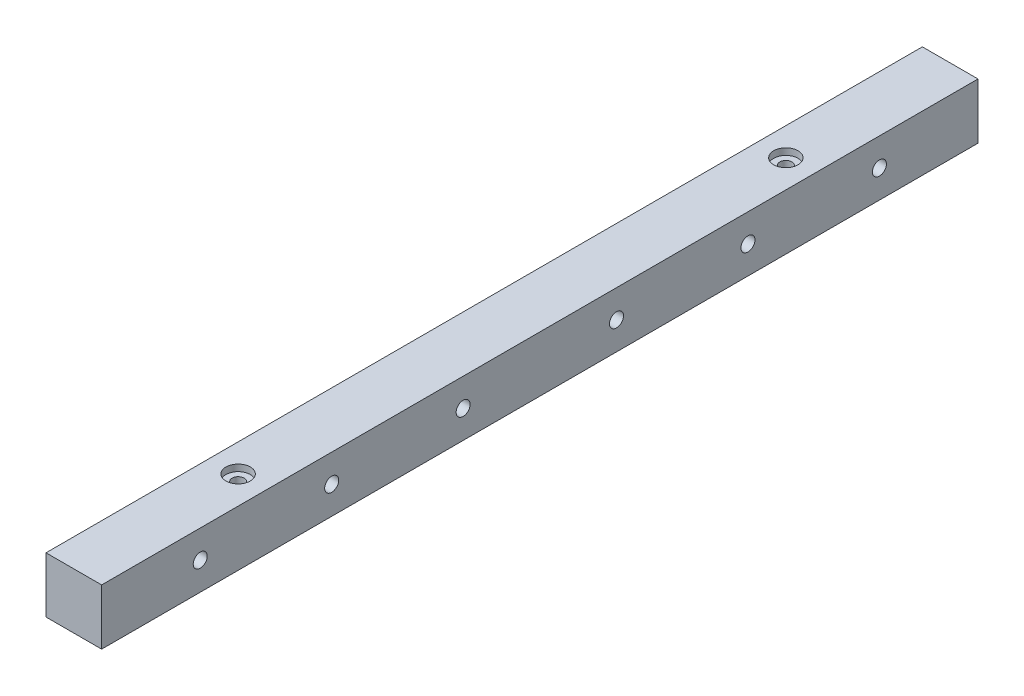
SolidWorks part; units mm, degrees
material "Delrin 2700 NC010, Low Viscosity Acetal Copolymer (SS)"
ref_plane "Front Plane" through (0, 0, 0) normal (0, 0, 1) x (1, 0, 0)
ref_plane "Top Plane" through (0, 0, 0) normal (0, 1, 0) x (1, 0, 0)
ref_plane "Right Plane" through (0, 0, 0) normal (1, 0, 0) x (0, 0, -1)
sketch "Sketch1" plane through (0, 0, 0) normal (0, 0, 1) x (1, 0, 0)
  line L0 (0, 0) -> (0, 25.6877) construction
  line L1 (12.7, -12.7) -> (-12.7, -12.7)
  line L2 (12.7, -12.7) -> (12.7, 12.7)
  line L3 (12.7, 12.7) -> (-12.7, 12.7)
  line L4 (-12.7, -12.7) -> (-12.7, 12.7)
  line L5 (0, 0) -> (36.1991, 0) construction
  dimension "D1" = 25.4
  dimension "D2" = 25.4
extrude "Boss-Extrude1" add sketch "Sketch1" along normal blind 200 and the other way blind 200
sketch "Sketch4" plane through (0, 0, 0) normal (1, 0, 0) x (0, 0, -1)
  line L0 (0, 0) -> (0, 23.5107) construction
  line L1 (-125, 23.5107) -> (-125, -37.5316) construction
  line L2 (-125, 23.5107) -> (0, 23.5107) construction
  line L3 (-125, -12.7) -> (-131, -12.7)
  line L4 (-131, -12.7) -> (-131, 2.3)
  line L5 (-131, 2.3) -> (-127.75, 4.1764)
  line L6 (-127.75, 4.1764) -> (-127.75, 9.7)
  line L7 (-127.75, 9.7) -> (-130.5563, 9.7)
  line L8 (-130.5563, 9.7) -> (-130.5563, 12.7)
  line L9 (-130.5563, 12.7) -> (-125, 12.7)
  line L10 (-125, 12.7) -> (-125, -12.7)
  line L11 (200, 12.7) -> (-200, 12.7) construction
  line L12 (200, -12.7) -> (-200, -12.7) construction
  dimension "D1" = 12
  dimension "D2" = 15
  dimension "D3" = 3
  dimension "D4" = 11.1125
  dimension "D5" = 5.5
  dimension "D6" = 60
  dimension "D7" = 250
revolve "Cut-Revolve1" cut sketch "Sketch4" angle 360 about L1
mirror "Mirror1" about plane through (0, 0, 0) normal (0, 0, 1) of "Cut-Revolve1"
sketch "Sketch5" plane through (12.7, 0, 0) normal (1, 0, 0) x (0, 0, -1)
  circle A0 centre (-155, 0) radius 3.2
  circle A1 centre (-95, 0) radius 3.2
  circle A2 centre (-35, 0) radius 3.2
  circle A3 centre (35, 0) radius 3.2
  circle A4 centre (95, 0) radius 3.2
  circle A5 centre (155, 0) radius 3.2
  circle A6 centre (155, 0) radius 3.2 construction
  circle A7 centre (95, 0) radius 3.2 construction
  circle A8 centre (35, 0) radius 3.2 construction
  circle A9 centre (-35, 0) radius 3.2 construction
  circle A10 centre (-95, 0) radius 3.2 construction
  circle A11 centre (-155, 0) radius 3.2 construction
extrude "Cut-Extrude1" cut sketch "Sketch5" against normal through all
sketch "Sketch6" plane through (-12.7, 0, 0) normal (-1, 0, 0) x (0, 0, 1)
  circle A0 centre (-155, 0) radius 4
  circle A1 centre (-95, 0) radius 4
  circle A2 centre (-35, 0) radius 4
  circle A3 centre (35, 0) radius 4
  circle A4 centre (95, 0) radius 4
  circle A5 centre (155, 0) radius 4
  circle A6 centre (-155, 0) radius 3.2 construction
  circle A7 centre (-95, 0) radius 3.2 construction
  circle A8 centre (-35, 0) radius 3.2 construction
  circle A9 centre (35, 0) radius 3.2 construction
  circle A10 centre (95, 0) radius 3.2 construction
  circle A11 centre (155, 0) radius 3.2 construction
  dimension "D1" = 8
extrude "Cut-Extrude2" cut sketch "Sketch6" against normal blind 3
